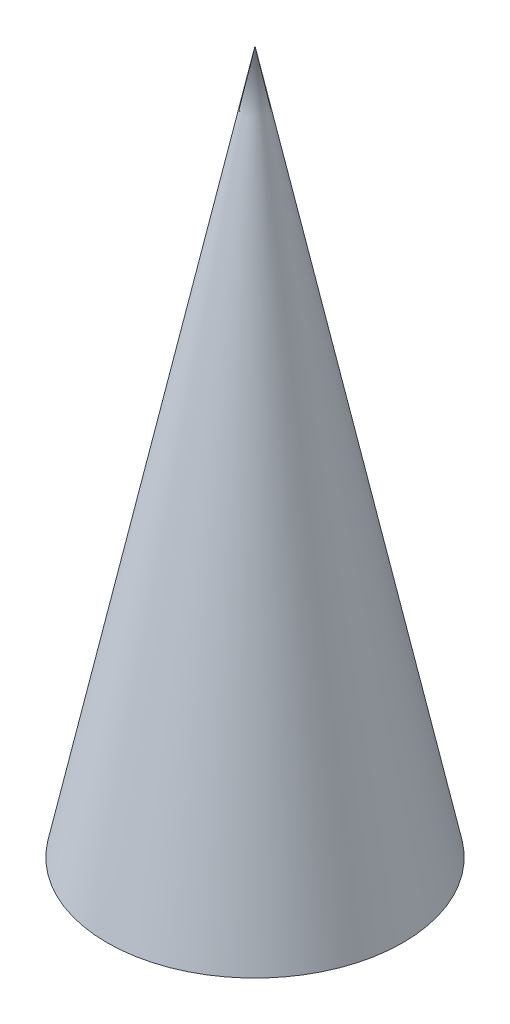
SolidWorks part; units mm, degrees
ref_plane "Спереди" through (0, 0, 0) normal (0, 0, 1) x (1, 0, 0)
ref_plane "Сверху" through (0, 0, 0) normal (0, 1, 0) x (1, 0, 0)
ref_plane "Справа" through (0, 0, 0) normal (1, 0, 0) x (0, 0, -1)
sketch "Эскиз1" plane through (0, 0, 0) normal (0, 1, 0) x (1, 0, 0)
  circle A0 centre (0, 0) radius 40
  dimension "D1" = 80
extrude "Вытянуть2" add sketch "Эскиз1" along normal blind 190
chamfer "Фаска1" distance 190 distance2 40 1 edges at (0, 190, 40) first distance on face at (0, 190, 40)
